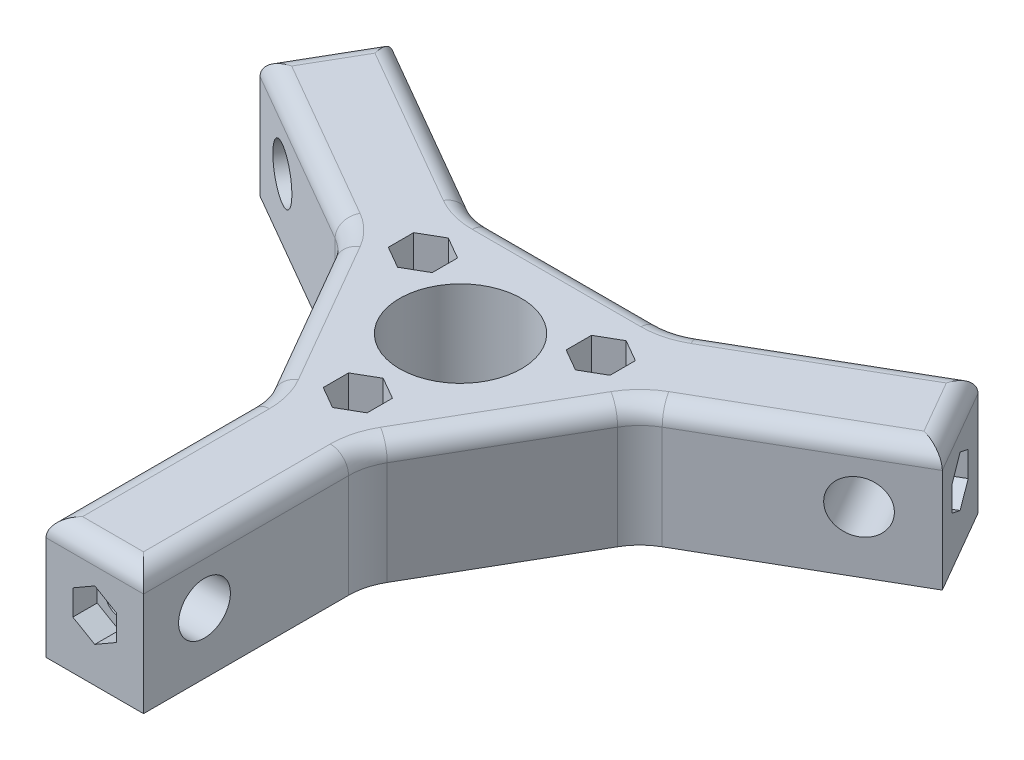
SolidWorks part; units mm, degrees
ref_plane "Front Plane" through (0, 0, 0) normal (0, 0, 1) x (1, 0, 0)
ref_plane "Top Plane" through (0, 0, 0) normal (0, 1, 0) x (1, 0, 0)
ref_plane "Right Plane" through (0, 0, 0) normal (1, 0, 0) x (0, 0, -1)
sketch "Sketch1" plane through (0, 0, 0) normal (0, 1, 0) x (1, 0, 0)
  line L0 (-103.923, -60) -> (0, 120) construction
  line L1 (0, 120) -> (103.923, -60) construction
  line L2 (103.923, -60) -> (-103.923, -60) construction
  line L3 (-8, -6) -> (-8, -60)
  line L4 (0, 0) -> (51.9615, 30) construction
  line L5 (0, 0) -> (0, -60) construction
  line L6 (0, 0) -> (-51.9615, 30) construction
  line L7 (-8, -60) -> (8, -60)
  line L8 (8, -60) -> (8, -6)
  line L9 (-8, -6) -> (8, -6) construction
  line L10 (1.1962, 9.9282) -> (9.1962, -3.9282) construction
  line L11 (47.9615, 36.9282) -> (55.9615, 23.0718)
  line L12 (55.9615, 23.0718) -> (9.1962, -3.9282)
  line L13 (1.1962, 9.9282) -> (47.9615, 36.9282)
  line L14 (-1.1962, 9.9282) -> (-9.1962, -3.9282) construction
  line L15 (-1.1962, 9.9282) -> (-47.9615, 36.9282)
  line L16 (-47.9615, 36.9282) -> (-55.9615, 23.0718)
  line L17 (-55.9615, 23.0718) -> (-9.1962, -3.9282)
  line L18 (16.5122, 18.7709) -> (-16.5122, 18.7709)
  line L19 (24.5122, 4.9145) -> (8, -23.6854)
  line L20 (-8, -23.6854) -> (-24.5122, 4.9145)
  circle A0 centre (0, 0) radius 10
  circle A2 centre (0, 0) radius 25
  dimension "D2" = 20
  dimension "D5" = 50
  dimension "D1" = 60
  dimension "D3" = 16
extrude "Boss-Extrude1" add sketch "Sketch1" along normal blind 20 contours A2 L15 L16 L17 | A2 L12 L11 L13 | A2 L3 L7 L8 | L3 A2 L8 A0 | L15 A2 L17 A0 | L12 A2 L13 A0 | L8 A2 L12 A0 | L17 A2 L3 A0 | L13 A2 L15 A0 region at (0, 0, 16.6445) region at (-13.5346, 0, 7.8142) region at (0, 0, 42.2811) region at (-14.4146, 0, -8.3223) region at (13.5346, 0, 7.8142) region at (-36.6165, 0, -21.1406) region at (0, 0, -15.6284) region at (14.4146, 0, -8.3223) region at (36.6165, 0, -21.1406)
ref_plane "Plane1" through (0, 0, 0) normal (0.5, 0, 0.866) x (0.866, 0, -0.5)
sketch "Sketch2" plane through (0, 0, 0) normal (0.5, 0, 0.866) x (0.866, 0, -0.5)
  line L1 (23.6854, 10) -> (60, 10) construction
  line L5 (23.6854, 0) -> (60, 0)
  line L6 (60, 0) -> (60, 20)
  line L7 (60, 20) -> (23.6854, 20)
  line L8 (23.6854, 20) -> (23.6854, 0)
  line L9 (23.6854, 0) -> (60, 0)
  line L10 (60, 0) -> (60, 20)
  line L11 (60, 20) -> (23.6854, 20)
  line L13 (23.6854, 20) -> (23.6854, 0)
  circle A0 centre (50, 10) radius 4.25
  dimension "D2" = 8.5
  dimension "D1" = 50
  dimension "D3" = 0
extrude "Cut-Extrude1" cut sketch "Sketch2" against normal up to next and the other way up to next contours A0
pattern_circular "CirPattern1" count 3 over 360 about axis through (0, 20, 0) along (0, -1, 0) of "Cut-Extrude1"
sketch "Sketch3" plane through (0, 20, 0) normal (0, 1, 0) x (1, 0, 0)
  line L0 (0, -23.6854) -> (0, -10) construction
  line L2 (-8, -23.6854) -> (8, -23.6854) construction
  line L3 (3.6, -18.9212) -> (3.6, -14.7643)
  line L4 (3.6, -14.7643) -> (0, -12.6858)
  line L5 (0, -12.6858) -> (-3.6, -14.7643)
  line L6 (-3.6, -14.7643) -> (-3.6, -18.9212)
  line L7 (-3.6, -18.9212) -> (0, -20.9996)
  line L8 (0, -20.9996) -> (3.6, -18.9212)
  line L9 (-55.9615, 23.0718) -> (-24.5122, 4.9145)
  line L11 (-55.9615, 23.0718) -> (-24.5122, 4.9145)
  line L15 (-24.5122, 4.9145) -> (-8, -23.6854)
  line L16 (-24.5122, 4.9145) -> (-8, -23.6854)
  line L17 (-8, -23.6854) -> (-8, -60)
  line L18 (-8, -23.6854) -> (-8, -60)
  line L19 (-8, -60) -> (8, -60)
  line L23 (-8, -60) -> (8, -60)
  line L24 (8, -60) -> (8, -23.6854)
  line L25 (8, -60) -> (8, -23.6854)
  line L26 (8, -23.6854) -> (24.5122, 4.9145)
  line L27 (8, -23.6854) -> (24.5122, 4.9145)
  line L28 (24.5122, 4.9145) -> (55.9615, 23.0718)
  line L29 (24.5122, 4.9145) -> (55.9615, 23.0718)
  line L35 (55.9615, 23.0718) -> (47.9615, 36.9282)
  line L36 (55.9615, 23.0718) -> (47.9615, 36.9282)
  line L37 (47.9615, 36.9282) -> (16.5122, 18.7709)
  line L38 (47.9615, 36.9282) -> (16.5122, 18.7709)
  line L39 (16.5122, 18.7709) -> (-16.5122, 18.7709)
  line L40 (16.5122, 18.7709) -> (-16.5122, 18.7709)
  line L41 (-16.5122, 18.7709) -> (-47.9615, 36.9282)
  line L42 (-16.5122, 18.7709) -> (-47.9615, 36.9282)
  line L43 (-47.9615, 36.9282) -> (-55.9615, 23.0718)
  line L44 (-47.9615, 36.9282) -> (-55.9615, 23.0718)
  circle A2 centre (0, -16.8427) radius 2.5
  circle A3 centre (0, 0) radius 10 construction
  circle A4 centre (0, -16.8427) radius 3.6 construction
  dimension "D2" = 7.2
  dimension "D3" = 5
  dimension "D1" = 0
sketch "Sketch4" plane through (0, 0, 60) normal (0, 0, 1) x (1, 0, 0)
  line L0 (0, 14.1569) -> (0, 10) construction
  line L1 (0, 14.1569) -> (-3.6, 12.0785)
  line L2 (-3.6, 12.0785) -> (-3.6, 7.9215)
  line L3 (-3.6, 7.9215) -> (0, 5.8431)
  line L4 (0, 5.8431) -> (3.6, 7.9215)
  line L5 (3.6, 7.9215) -> (3.6, 12.0785)
  line L6 (3.6, 12.0785) -> (0, 14.1569)
  line L7 (0, 20) -> (0, 0) construction
  line L8 (-8, 20) -> (8, 20) construction
  circle A0 centre (0, 10) radius 2.25
  circle A1 centre (0, 10) radius 3.6 construction
  dimension "D1" = 4.5
  dimension "D3" = 7.2
extrude "Cut-Extrude4" cut sketch "Sketch4" against normal up to surface (5.75 mm away) contours A0 up to face at (-8, 10, 45.75)
extrude "Cut-Extrude5" cut sketch "Sketch4<3>" against normal blind 4 contours L5 L6 L1 L2 L3 L4
sketch "Sketch4<3>" plane through (0, 0, 60) normal (0, 0, 1) x (1, 0, 0) same geometry as "Sketch4"
extrude "Cut-Extrude6" cut sketch "Sketch3" against normal blind 10 contours L3 L4 L5 L6 L7 L8
extrude "Cut-Extrude7" cut sketch "Sketch3<7>" against normal through all from surface contours A2 starting at face at (0, 10, 16.8427)
sketch "Sketch3<7>" plane through (0, 20, 0) normal (0, 1, 0) x (1, 0, 0) same geometry as "Sketch3"
pattern_circular "CirPattern2" count 3 over 360 about axis through (0, 20, 0) along (0, 1, 0) of "Cut-Extrude6", "Cut-Extrude7"
fillet "Fillet1" radius 10 6 edges at (8, 10, 23.6854) (-16.5122, 10, -18.7709) (16.5122, 10, -18.7709) (24.5122, 10, -4.9145) (-8, 10, 23.6854) (-24.5122, 10, -4.9145)
fillet "Fillet2" radius 3 18 edges at (41.3971, 20, -14.663) (24.7616, 20, -4.6651) (16.2561, 20, 9.3855) (8.3407, 20, 23.7767) (33.3971, 20, -28.5194) (16.4209, 20, -19.1117) (0, 20, -18.7709) (-16.4209, 20, -19.1117) (-8, 20, 43.1825) (-8.3407, 20, 23.7767) (-16.2561, 20, 9.3855) (-24.7616, 20, -4.6651) (-51.9615, 20, -30) (51.9615, 20, -30) (0, 20, 60) (8, 20, 43.1825) (-33.3971, 20, -28.5194) (-41.3971, 20, -14.663)
pattern_circular "CirPattern3" count 3 over 360 about axis through (0, 20, 0) along (0, -1, 0) of "Cut-Extrude4", "Cut-Extrude5"
ref_point "Point1"
ref_point "Point2"
sketch "Sketch5" plane through (0, 0, 0) normal (0, -1, 0) x (1, 0, 0)
  line L0 (-23.1724, -2.594) -> (-13.8327, -18.7709)
  line L1 (-9.3397, 21.3649) -> (9.3397, 21.3649)
  line L2 (23.1724, -2.594) -> (13.8327, -18.7709)
  line L3 (-23.1724, -2.594) -> (-9.3397, 21.3649)
  line L4 (9.3397, 21.3649) -> (23.1724, -2.594)
  line L5 (13.8327, -18.7709) -> (-13.8327, -18.7709)
  line L12 (-26.8327, -6.2543) -> (-55.9615, -23.0718)
  line L13 (-55.9615, -23.0718) -> (-47.9615, -36.9282)
  line L14 (-47.9615, -36.9282) -> (-18.8327, -20.1107)
  line L15 (-13.8327, -18.7709) -> (13.8327, -18.7709)
  line L16 (18.8327, -20.1107) -> (47.9615, -36.9282)
  line L17 (47.9615, -36.9282) -> (55.9615, -23.0718)
  line L18 (55.9615, -23.0718) -> (26.8327, -6.2543)
  line L19 (23.1724, -2.594) -> (9.3397, 21.3649)
  line L20 (8, 26.3649) -> (8, 60)
  line L21 (8, 60) -> (-8, 60)
  line L22 (-8, 60) -> (-8, 26.3649)
  line L23 (-9.3397, 21.3649) -> (-23.1724, -2.594)
  line L24 (-26.8327, -6.2543) -> (-55.9615, -23.0718)
  line L25 (-55.9615, -23.0718) -> (-47.9615, -36.9282)
  line L26 (-47.9615, -36.9282) -> (-18.8327, -20.1107)
  line L27 (-13.8327, -18.7709) -> (13.8327, -18.7709)
  line L28 (18.8327, -20.1107) -> (47.9615, -36.9282)
  line L29 (47.9615, -36.9282) -> (55.9615, -23.0718)
  line L30 (55.9615, -23.0718) -> (26.8327, -6.2543)
  line L31 (23.1724, -2.594) -> (9.3397, 21.3649)
  line L32 (8, 26.3649) -> (8, 60)
  line L33 (8, 60) -> (-8, 60)
  line L34 (-8, 60) -> (-8, 26.3649)
  line L35 (-9.3397, 21.3649) -> (-23.1724, -2.594)
  circle A0 centre (0, 16.8427) radius 2.5 construction
  circle A1 centre (14.5862, -8.4214) radius 2.5 construction
  circle A2 centre (-14.5862, -8.4214) radius 2.5 construction
  circle A3 centre (0, 16.8427) radius 2.5
  circle A4 centre (14.5862, -8.4214) radius 2.5
  circle A5 centre (-14.5862, -8.4214) radius 2.5
  arc A6 (-13.8327, -18.7709) -> (-18.8327, -20.1107) centre (-13.8327, -28.7709) ccw
  arc A7 (18.8327, -20.1107) -> (13.8327, -18.7709) centre (13.8327, -28.7709) ccw
  arc A8 (23.1724, -2.594) -> (26.8327, -6.2543) centre (31.8327, 2.406) ccw
  arc A9 (8, 26.3649) -> (9.3397, 21.3649) centre (18, 26.3649) ccw
  arc A10 (-9.3397, 21.3649) -> (-8, 26.3649) centre (-18, 26.3649) ccw
  arc A11 (-26.8327, -6.2543) -> (-23.1724, -2.594) centre (-31.8327, 2.406) ccw
  arc A12 (-13.8327, -18.7709) -> (-18.8327, -20.1107) centre (-13.8327, -28.7709) ccw
  arc A13 (18.8327, -20.1107) -> (13.8327, -18.7709) centre (13.8327, -28.7709) ccw
  arc A14 (23.1724, -2.594) -> (26.8327, -6.2543) centre (31.8327, 2.406) ccw
  arc A15 (8, 26.3649) -> (9.3397, 21.3649) centre (18, 26.3649) ccw
  arc A16 (-9.3397, 21.3649) -> (-8, 26.3649) centre (-18, 26.3649) ccw
  arc A17 (-26.8327, -6.2543) -> (-23.1724, -2.594) centre (-31.8327, 2.406) ccw
  circle A18 centre (0, 0) radius 10
  circle A19 centre (0, 16.8427) radius 2.5
  circle A20 centre (14.5862, -8.4214) radius 2.5
  circle A21 centre (-14.5862, -8.4214) radius 2.5
  dimension "D2" = 20
  dimension "D1" = 0
